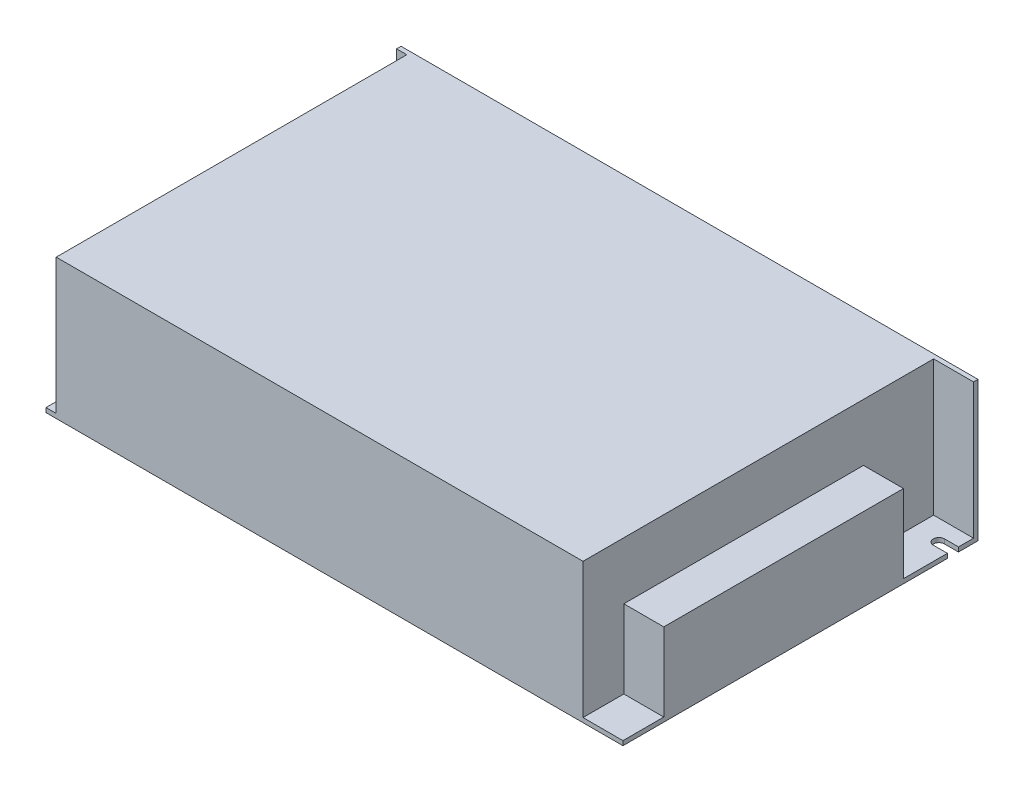
SolidWorks part; units mm, degrees
ref_plane "Front Plane" through (0, 0, 0) normal (0, 0, 1) x (1, 0, 0)
ref_plane "Top Plane" through (0, 0, 0) normal (0, 1, 0) x (1, 0, 0)
ref_plane "Right Plane" through (0, 0, 0) normal (1, 0, 0) x (0, 0, -1)
sketch "Sketch1" plane through (0, 0, 0) normal (0, 1, 0) x (1, 0, 0)
  line L1 (0, 0) -> (165.1, 0)
  line L2 (0, 0) -> (0, 101.6)
  line L3 (0, 101.6) -> (165.1, 101.6)
  line L4 (165.1, 0) -> (165.1, 101.6)
  dimension "D1" = 101.6
  dimension "D2" = 165.1
extrude "Boss-Extrude1" add sketch "Sketch1" along normal blind 40
sketch "Sketch2" plane through (165.1, 0, 0) normal (1, 0, 0) x (0, 0, -1)
  line L0 (0, 0) -> (101.6, 0) construction
  line L1 (0, 40) -> (100.33, 40)
  line L2 (0, 40) -> (0, 1.27)
  line L3 (0, 1.27) -> (100.33, 1.27)
  line L4 (100.33, 40) -> (100.33, 1.27)
  line L5 (0, 40) -> (100.33, 1.27) construction
  line L6 (0, 1.27) -> (100.33, 40) construction
  line L7 (101.6, 40) -> (101.6, 0) construction
  point P4 (50.165, 20.635)
  dimension "D1" = 1.27
  dimension "D2" = 1.27
extrude "Cut-Extrude1" cut sketch "Sketch2" against normal blind 11.43 contours L3 L4 L1 L2
sketch "Sketch3" plane through (0, 0, 0) normal (-1, 0, 0) x (0, 0, 1)
  line L4 (0, 1.27) -> (0, 40)
  line L5 (-100.33, 1.27) -> (0, 1.27)
  line L6 (-100.33, 40) -> (-100.33, 1.27)
  line L7 (0, 40) -> (-100.33, 40)
  line L8 (0, 1.27) -> (0, 40)
  line L9 (-100.33, 1.27) -> (0, 1.27)
  line L10 (-100.33, 40) -> (-100.33, 1.27)
  line L11 (0, 40) -> (-100.33, 40)
  dimension "D1" = 0
extrude "Cut-Extrude2" cut sketch "Sketch3" against normal blind 2.921
sketch "Sketch4" plane through (0, 1.27, 0) normal (0, 1, 0) x (1, 0, 0)
  line L0 (165.1, 0) -> (165.1, 100.33) construction
  line L1 (165.1, 11.684) -> (153.67, 11.684)
  line L2 (165.1, 11.684) -> (165.1, 80.264)
  line L3 (165.1, 80.264) -> (153.67, 80.264)
  line L4 (153.67, 11.684) -> (153.67, 80.264)
  line L5 (165.1, 11.684) -> (153.67, 80.264) construction
  line L6 (165.1, 80.264) -> (153.67, 11.684) construction
  line L7 (153.67, 0) -> (153.67, 100.33) construction
  line L8 (153.67, 0) -> (165.1, 0) construction
  point P4 (159.385, 45.974)
  dimension "D1" = 68.58
  dimension "D2" = 11.684
extrude "Boss-Extrude2" add sketch "Sketch4" along normal blind 22.352
sketch "Sketch5" plane through (0, 1.27, 0) normal (0, 1, 0) x (1, 0, 0)
  line L0 (0, 8.255) -> (0, 5.08)
  line L1 (0, 100.33) -> (0, 0) construction
  line L2 (0, 5.08) -> (4.0005, 5.08)
  line L3 (4.0005, 8.255) -> (0, 8.255)
  line L4 (165.1, 92.837) -> (165.1, 96.012)
  line L5 (165.1, 80.264) -> (165.1, 100.33) construction
  line L6 (165.1, 96.012) -> (161.0995, 96.012)
  line L7 (161.0995, 92.837) -> (165.1, 92.837)
  line L8 (165.1, 101.6) -> (0, 101.6) construction
  line L9 (2.921, 0) -> (0, 0) construction
  arc A0 (4.0005, 5.08) -> (4.0005, 8.255) centre (4.0005, 6.6675) ccw
  arc A1 (161.0995, 96.012) -> (161.0995, 92.837) centre (161.0995, 94.4245) ccw
  dimension "D2" = 5.588
  dimension "D1" = 3.175
  dimension "D3" = 5.588
  dimension "D4" = 5.08
extrude "Cut-Extrude3" cut sketch "Sketch5" against normal blind 22.352
sketch "Sketch6" plane through (0, 0, 0) normal (0, -1, 0) x (1, 0, 0)
  line L1 (165.1, 0) -> (165.1, -92.837) construction
  line L2 (0, 0) -> (165.1, 0) construction
  circle A0 centre (63.246, -65.278) radius 1.27
  circle A1 centre (140.97, -65.278) radius 1.27
  dimension "D1" = 80.264
  dimension "D2" = 64.008
  dimension "D3" = 22.86
  dimension "D4" = 2.54
extrude "Cut-Extrude4" cut sketch "Sketch6" against normal blind 10.16
